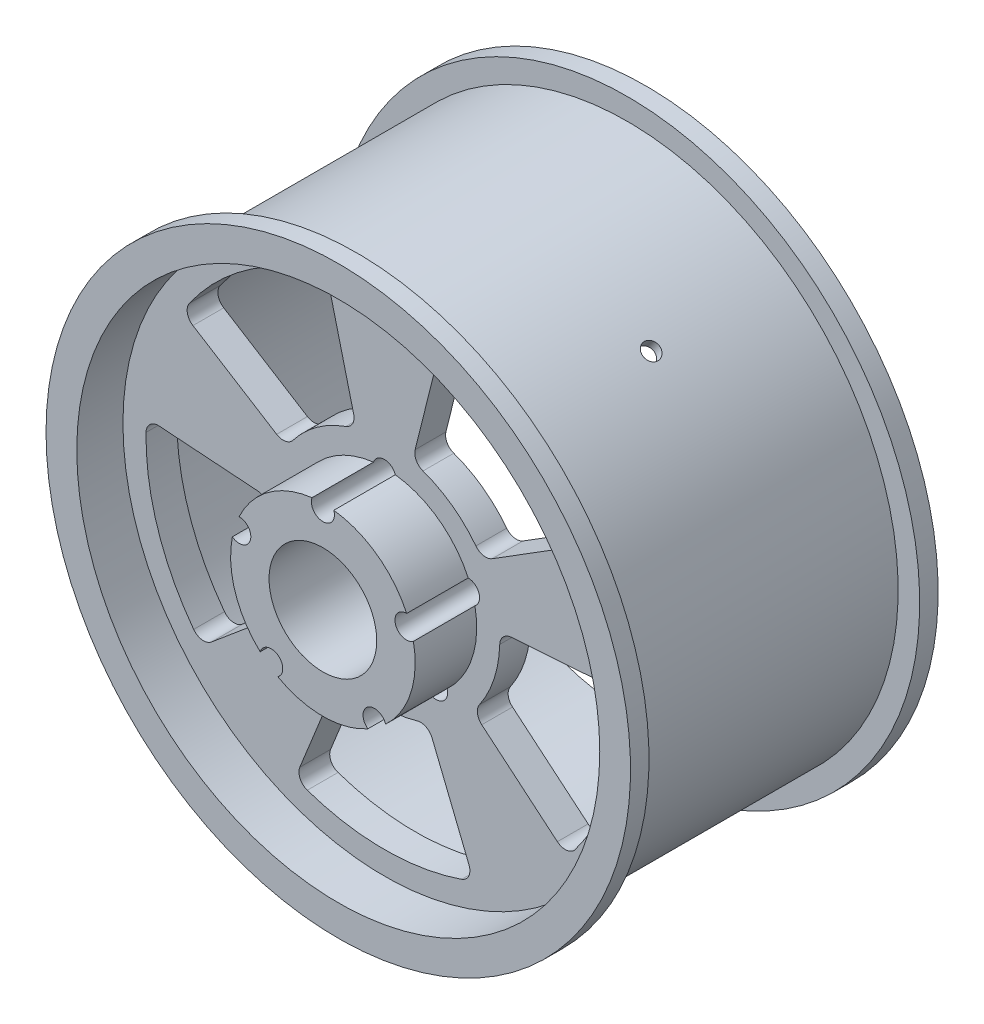
SolidWorks part; units mm, degrees
ref_plane "前视基准面" through (0, 0, 0) normal (0, 0, 1) x (1, 0, 0)
ref_plane "上视基准面" through (0, 0, 0) normal (0, 1, 0) x (1, 0, 0)
ref_plane "右视基准面" through (0, 0, 0) normal (1, 0, 0) x (0, 0, -1)
sketch "草图1" plane through (0, 0, 0) normal (0, 1, 0) x (1, 0, 0)
  line L0 (0, 0) -> (0, -200) construction
  line L1 (170, 0) -> (190, 0)
  line L2 (190, 0) -> (190, -12)
  line L3 (190, -12) -> (176, -12)
  line L4 (176, -12) -> (176, -188)
  line L5 (176, -188) -> (190, -188)
  line L6 (190, -188) -> (190, -200)
  line L7 (190, -200) -> (170, -200)
  line L8 (170, -200) -> (170, 0)
revolve "旋转1" add sketch "草图1" angle 360 about L0
sketch "草图2" plane through (0, 0, 0) normal (0, 1, 0) x (1, 0, 0)
  line L0 (0, -140) -> (0, -210) construction
  line L1 (0, -140) -> (60, -140)
  line L2 (60, -140) -> (60, -150)
  line L3 (60, -150) -> (171, -150)
  line L4 (171, -150) -> (171, -170)
  line L5 (171, -170) -> (60, -170)
  line L6 (60, -170) -> (60, -210)
  line L7 (60, -210) -> (0, -210)
  line L8 (0, -210) -> (0, -140)
revolve "旋转2" add sketch "草图2" angle 360 about L0
ref_plane "基准面1" through (0, 0, 210) normal (0, 0, 1) x (1, 0, 0)
sketch "草图3" plane through (0, 0, 210) normal (0, 0, 1) x (1, 0, 0)
  circle A0 centre (0, 57.15) radius 7.5
  circle A1 centre (-54.3529, 17.6603) radius 7.5
  circle A2 centre (-33.5919, -46.2353) radius 7.5
  circle A3 centre (33.5919, -46.2353) radius 7.5
  circle A4 centre (54.3529, 17.6603) radius 7.5
extrude "切除-拉伸1" cut sketch "草图3" against normal through all
sketch "草图4" plane through (0, 0, 210) normal (0, 0, 1) x (1, 0, 0)
  circle A0 centre (0, 0) radius 35
extrude "切除-拉伸2" cut sketch "草图4" against normal through all
ref_plane "基准面2" through (0, 0, 150) normal (0, 0, 1) x (1, 0, 0)
ref_axis "基准轴1" through (0, 0, 220.5) along (0, 0, -1)
sketch3d "3D草图1"
  line L0 (94.046, 129.443, 100) -> (124.876, 171.912, 100)
sweep "切除-扫描2" cut path "3D草图1" circular profile diameter 11 parameters "D3"=11
sketch "草图13" plane through (0, 0, 150) normal (0, 0, 1) x (1, 0, 0)
  line L0 (19.985, 80.154) -> (35.509, 142.42)
  line L1 (124.477, 77.781) -> (70.055, 43.775)
  arc A0 (59.473, 45.694) -> (25.08, 70.685) centre (-0.023, -0.0238) ccw
  arc A1 (25.08, 70.685) -> (19.985, 80.154) centre (27.7697, 78.2375) cw
  arc A2 (35.509, 142.42) -> (45.634, 148.148) centre (43.2631, 140.5262) cw
  arc A3 (45.634, 148.148) -> (126.78, 89.173) centre (-0.1095, -0.1058) cw
  arc A4 (126.78, 89.173) -> (124.477, 77.781) centre (120.2225, 84.5699) cw
  arc A5 (70.055, 43.775) -> (59.473, 45.694) centre (65.8241, 50.5801) cw
extrude "切除-拉伸4" cut sketch "草图13" along normal blind 20
pattern_circular "阵列(圆周)2" count 5 over 360 about axis through (0, 0, 220.5) along (0, 0, -1) of "切除-拉伸4"
